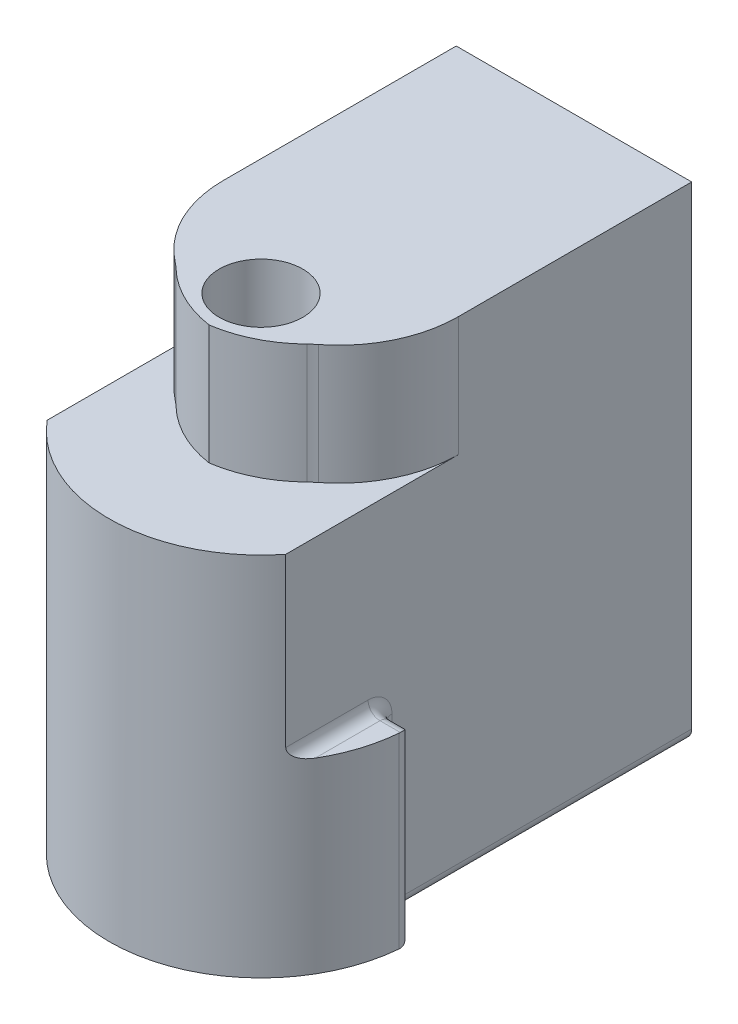
SolidWorks part; units mm, degrees
ref_plane "Front Plane" through (0, 0, 0) normal (0, 0, 1) x (1, 0, 0)
ref_plane "Top Plane" through (0, 0, 0) normal (0, 1, 0) x (1, 0, 0)
ref_plane "Right Plane" through (0, 0, 0) normal (1, 0, 0) x (0, 0, -1)
sketch "Sketch2" plane through (0, -2111.3899, 0) normal (0, 1, 0) x (1, 0, 0)
  circle A1 centre (-53.694, 163.8403) radius 12.7
extrude "Boss-Extrude6" add sketch "Sketch2" along normal blind 40.64
sketch "Sketch3" plane through (0, -2070.7499, 0) normal (0, 1, 0) x (1, 0, 0)
  circle A0 centre (-53.694, 163.8403) radius 3.5
  dimension "D1" = 7
extrude "Cut-Extrude1" cut sketch "Sketch3" against normal up to surface (40.64 mm away) up to face at (-66.394, -2111.3899, -163.8403)
sketch "Sketch4" plane through (0, -2111.3899, 0) normal (0, -1, 0) x (1, 0, 0)
  circle A0 centre (-61.9429, -159.0778) radius 1.778
  circle A2 centre (-53.694, -173.3653) radius 1.778
  circle A3 centre (-45.4451, -159.0778) radius 1.778
extrude "Cut-Extrude2" cut sketch "Sketch4" against normal blind 6
sketch "Sketch7" plane through (0, -2111.3899, 0) normal (0, -1, 0) x (1, 0, 0)
  line L9 (-40.994, -163.8403) -> (-40.994, -182.6343)
  line L10 (-40.994, -182.6343) -> (-66.1797, -182.6343)
  line L11 (-66.1797, -166.1636) -> (-66.1797, -182.6343)
  circle A0 centre (-53.694, -163.8403) radius 12.7 construction
  arc A1 (-66.1797, -166.1636) -> (-40.994, -163.8403) centre (-53.694, -163.8403) ccw
extrude "Boss-Extrude8" add sketch "Sketch7" against normal blind 10
sketch "Sketch8" plane through (0, 0, -182.6343) normal (0, 0, -1) x (-1, 0, 0)
  line L0 (40.994, -2101.3899) -> (40.994, -2111.3899) construction
  line L1 (40.994, -2101.3899) -> (66.1797, -2101.3899)
  line L2 (40.994, -2101.3899) -> (40.994, -2111.3899)
  line L3 (40.994, -2111.3899) -> (66.1797, -2111.3899)
  line L4 (66.1797, -2101.3899) -> (66.1797, -2111.3899)
  line L5 (66.1797, -2101.3899) -> (40.994, -2101.3899) construction
  line L6 (66.1797, -2111.3899) -> (40.994, -2111.3899) construction
  line L7 (66.1797, -2101.3899) -> (66.1797, -2111.3899) construction
extrude "Boss-Extrude9" add sketch "Sketch8" along normal up to surface (7.2848 mm away)
sketch "Sketch9" plane through (0, -2070.7499, 0) normal (0, 1, 0) x (1, 0, 0)
  line L0 (-40.994, 189.9191) -> (-40.994, 163.8403) construction
  line L2 (-66.1797, 163.8403) -> (-66.1797, 189.9191)
  line L3 (-66.1797, 189.9191) -> (-40.994, 189.9191)
  line L4 (-40.994, 163.8403) -> (-40.994, 189.9191)
  line L5 (-66.1797, 166.1636) -> (-66.1797, 189.9191) construction
  arc A0 (-40.994, 163.8403) -> (-66.1797, 163.8403) centre (-53.5868, 163.8403) ccw
extrude "Boss-Extrude10" add sketch "Sketch9" against normal up to surface (30.64 mm away) up to face at (-53.322, -2101.3899, -180.3317)
hole_wizard "CSK for M3 Flat Head Machine Screw1" positions "Sketch14" profile "Sketch15" countersink size "M3" standard "ANSI Metric"
sketch "Sketch14" plane through (0, 0, -189.9191) normal (0, 0, -1) x (-1, 0, 0)
  point P10 (53.5868, -2075.7499)
  point P12 (62.6264, -2075.7499)
  point P14 (44.5473, -2075.7499)
sketch "Sketch15" plane through (-53.5868, -2075.7499, -189.9191) normal (1, 0, 0) x (0, 1, 0)
  line L0 (0, 0) -> (0, 10)
  line L1 (0, 10) -> (1.7, 8.9785)
  line L2 (1.7, 8.9785) -> (1.7, 1.45)
  line L3 (1.7, 1.45) -> (3.15, 0)
  line L5 (3.15, 0) -> (0, 0)
  line L6 (-1.7, 1.45) -> (-3.15, 0) construction
  line L10 (0, 10) -> (-1.7, 8.9785) construction
  line L11 (0, -6.35) -> (0, 107.95) construction
  dimension "Hole Dia." = 3.4
  dimension "Hole Depth" = 10
  dimension "Near C'Sink Dia." = 6.3
  dimension "Near C'Sink Angle" = 90
  dimension "Drill Angle" = 118
ref_plane "Plane1" through (0, -2091.0699, 0) normal (0, 1, 0) x (1, 0, 0)
mirror "Mirror1" about plane through (0, -2091.0699, 0) normal (0, 1, 0) of "CSK for M3 Flat Head Machine Screw1"
sketch "Sketch16" plane through (0, -2070.7499, 0) normal (0, 1, 0) x (1, 0, 0)
  line L0 (-53.694, 151.1403) -> (-53.694, 163.1403) construction
  line L1 (-53.694, 151.1403) -> (-61.6485, 151.1403) construction
  line L2 (-57.6712, 151.1403) -> (-57.6712, 176.4403) construction
  line L3 (-53.694, 163.1403) -> (-66.3747, 163.1403) construction
  line L5 (-67.2059, 176.4403) -> (-63.4359, 176.4403)
  line L6 (-67.2059, 176.4403) -> (-67.2059, 154.4394)
  line L7 (-67.2059, 154.4394) -> (-63.4359, 154.4394)
  line L8 (-63.4359, 176.4403) -> (-63.4359, 154.4394)
  line L9 (-40.994, 163.8403) -> (-40.994, 189.9191) construction
  line L11 (-53.5868, 189.9191) -> (-53.5868, 168.4351) construction
  line L12 (-40.994, 189.9191) -> (-66.1797, 189.9191) construction
  line L13 (-53.4797, 163.1403) -> (-40.799, 163.1403) construction
  line L18 (-39.9677, 154.4394) -> (-43.7377, 154.4394)
  line L19 (-39.9677, 176.4403) -> (-39.9677, 154.4394)
  line L20 (-39.9677, 176.4403) -> (-43.7377, 176.4403)
  line L21 (-43.7377, 176.4403) -> (-43.7377, 154.4394)
  arc A0 (-66.1797, 166.1636) -> (-40.994, 163.8403) centre (-53.694, 163.8403) ccw construction
  dimension "D1" = 1.0262
  dimension "D2" = 25.3
  dimension "D3" = 16.6773
  dimension "D4" = 2.7438
  dimension "D5" = 26.7787
extrude "Cut-Extrude3" cut sketch "Sketch16" against normal blind 25
sketch "Sketch17" plane through (-66.1797, 0, 0) normal (-1, 0, 0) x (0, 0, 1)
  line L1 (-176.4403, -2095.7499) -> (-166.1636, -2095.7499)
  line L2 (-176.4403, -2095.7499) -> (-176.4403, -2111.3899)
  line L3 (-176.4403, -2111.3899) -> (-166.1636, -2111.3899)
  line L4 (-166.1636, -2095.7499) -> (-166.1636, -2111.3899)
extrude "Cut-Extrude4" cut sketch "Sketch17" against normal up to surface (2.7438 mm away) up to face at (-63.4359, -2083.2499, -166.0665)
sketch "Sketch18" plane through (-40.994, 0, 0) normal (1, 0, 0) x (0, 0, -1)
  line L1 (176.4403, -2095.7499) -> (163.8403, -2095.7499)
  line L2 (176.4403, -2095.7499) -> (176.4403, -2111.3899)
  line L3 (176.4403, -2111.3899) -> (163.8403, -2111.3899)
  line L4 (163.8403, -2095.7499) -> (163.8403, -2111.3899)
extrude "Cut-Extrude5" cut sketch "Sketch18" against normal up to surface (2.7438 mm away) up to face at (-43.7377, -2083.2499, -166.1981)
sketch "Sketch20" plane through (0, -2070.7499, 0) normal (0, 1, 0) x (1, 0, 0)
  line L0 (-63.4359, 176.4403) -> (-66.1797, 176.4403) construction
  line L1 (-43.7377, 176.4403) -> (-40.994, 176.4403)
  line L2 (-43.7377, 176.4403) -> (-43.7377, 189.9191)
  line L3 (-43.7377, 189.9191) -> (-40.994, 189.9191)
  line L4 (-40.994, 176.4403) -> (-40.994, 189.9191)
  line L5 (-63.4359, 176.4403) -> (-66.1797, 176.4403)
  line L6 (-63.4359, 176.4403) -> (-63.4359, 189.9191)
  line L7 (-63.4359, 189.9191) -> (-66.1797, 189.9191)
  line L8 (-66.1797, 176.4403) -> (-66.1797, 189.9191)
extrude "Cut-Extrude7" cut sketch "Sketch20" against normal blind 25
sketch "Sketch21" plane through (0, 0, -189.9191) normal (0, 0, -1) x (-1, 0, 0)
  line L0 (63.4359, -2095.7499) -> (63.4359, -2078.7941) construction
  line L1 (43.7377, -2070.7499) -> (49.4792, -2070.7499)
  line L2 (43.7377, -2070.7499) -> (43.7377, -2082.4464)
  line L3 (43.7377, -2082.4464) -> (49.4792, -2082.4464)
  line L4 (63.4359, -2070.7499) -> (63.4359, -2082.4464)
  line L5 (57.4971, -2082.4464) -> (57.4971, -2070.7499)
  line L6 (49.4792, -2082.4464) -> (49.4792, -2070.7499)
  line L7 (57.4971, -2082.4464) -> (63.4359, -2082.4464)
  line L8 (57.4971, -2070.7499) -> (63.4359, -2070.7499)
  line L9 (43.7377, -2072.7057) -> (43.7377, -2070.7499) construction
  line L10 (43.7377, -2070.7499) -> (63.4359, -2070.7499) construction
  dimension "D1" = 5.7415
  dimension "D2" = 13.7594
  dimension "D3" = 11.6965
extrude "Boss-Extrude12" add sketch "Sketch21" against normal blind 15
sketch "Sketch22" plane through (0, -2070.7499, 0) normal (0, 1, 0) x (1, 0, 0)
  line L0 (-53.694, 159.2557) -> (-57.3241, 159.2557)
  line L1 (-63.4359, 155.6927) -> (-63.4359, 166.1636) construction
  line L2 (-53.694, 159.2557) -> (-49.75, 159.2557)
  line L3 (-43.7377, 163.8403) -> (-43.7377, 155.956) construction
  line L4 (-43.7377, 159.2557) -> (-43.7377, 155.956)
  line L5 (-63.4359, 159.2557) -> (-63.4359, 155.6927)
  line L6 (-57.194, 163.8403) -> (-63.4359, 163.8403) construction
  line L7 (-63.4359, 155.6927) -> (-63.4359, 189.9191) construction
  line L8 (-63.4359, 163.8403) -> (-63.4359, 159.2557)
  line L9 (-43.7377, 163.8403) -> (-43.7377, 159.2557)
  arc A0 (-58.2786, 163.8403) -> (-53.694, 159.2557) centre (-53.694, 163.8403) ccw
  arc A1 (-63.4359, 155.6927) -> (-43.7377, 155.956) centre (-53.694, 163.8403) ccw
  circle A2 centre (-53.694, 163.8403) radius 3.5 construction
  arc A3 (-57.3241, 159.2557) -> (-63.4359, 163.8403) centre (-63.4359, 157.4742) ccw
  arc A4 (-43.7377, 163.8403) -> (-49.75, 159.2557) centre (-43.7377, 157.6058) ccw
  line M6 (-63.4359, 189.9191) -> (-63.4359, 155.6927)
  arc M7 (-63.4359, 155.6927) -> (-43.7377, 155.956) centre (-53.694, 163.8403) ccw
  line M8 (-43.7377, 155.956) -> (-43.7377, 189.9191)
  dimension "D1" = 4.5846
extrude "Cut-Extrude8" cut sketch "Sketch22" against normal blind 10 contours A4 L2 L0 A3 M8 M6 M7 region at (-53.6343, -2070.7499, -157.0534)
fillet "Fillet1" radius 10 2 edges at (-49.75, -2075.7499, -159.2557) (-57.3241, -2075.7499, -159.2557)
fillet "Fillet5" radius 10 2 edges at (-63.4359, -2075.7499, -163.8403) (-43.7377, -2075.7499, -163.8403)
sketch "Sketch23" plane through (0, -2095.7499, 0) normal (0, 1, 0) x (1, 0, 0)
  line L1 (-63.4359, 189.9191) -> (-66.1797, 189.9191)
  line L2 (-63.4359, 189.9191) -> (-63.4359, 176.4403)
  line L3 (-63.4359, 176.4403) -> (-66.1797, 176.4403)
  line L4 (-66.1797, 189.9191) -> (-66.1797, 176.4403)
  line L5 (-43.7377, 189.9191) -> (-40.994, 189.9191)
  line L6 (-43.7377, 189.9191) -> (-43.7377, 176.4403)
  line L7 (-43.7377, 176.4403) -> (-40.994, 176.4403)
  line L8 (-40.994, 189.9191) -> (-40.994, 176.4403)
extrude "Cut-Extrude9" cut sketch "Sketch23" against normal blind 20
sketch "Sketch24" plane through (0, 0, -189.9191) normal (0, 0, -1) x (-1, 0, 0)
  line L0 (43.7377, -2103.3457) -> (43.7377, -2070.7499) construction
  line L1 (43.7377, -2102.0691) -> (49.2953, -2102.0691)
  line L2 (43.7377, -2102.0691) -> (43.7377, -2111.3899)
  line L3 (43.7377, -2111.3899) -> (49.2953, -2111.3899)
  line L4 (49.2953, -2102.0691) -> (49.2953, -2111.3899)
  line L5 (63.4359, -2111.3899) -> (43.7377, -2111.3899) construction
  line L6 (63.4359, -2103.3457) -> (63.4359, -2070.7499) construction
  line L7 (63.4359, -2102.0691) -> (58.1762, -2102.0691)
  line L8 (63.4359, -2102.0691) -> (63.4359, -2111.3899)
  line L9 (63.4359, -2111.3899) -> (58.1762, -2111.3899)
  line L10 (58.1762, -2102.0691) -> (58.1762, -2111.3899)
extrude "Boss-Extrude13" add sketch "Sketch24" against normal blind 20
fillet "Fillet6" radius 1 12 edges at (-63.4359, -2111.3899, -178.0413) (-63.4359, -2095.7499, -160.9281) (-43.7377, -2095.7499, -159.8981) (-43.7377, -2111.3899, -176.8797) (-63.4359, -2103.5699, -166.1636) (-64.8078, -2095.7499, -166.1636) (-66.1797, -2103.5699, -166.1636) (-64.8078, -2111.3899, -166.1636) (-43.7377, -2103.5699, -163.8403) (-42.3658, -2111.3899, -163.8403) (-40.994, -2103.5699, -163.8403) (-42.3658, -2095.7499, -163.8403)
